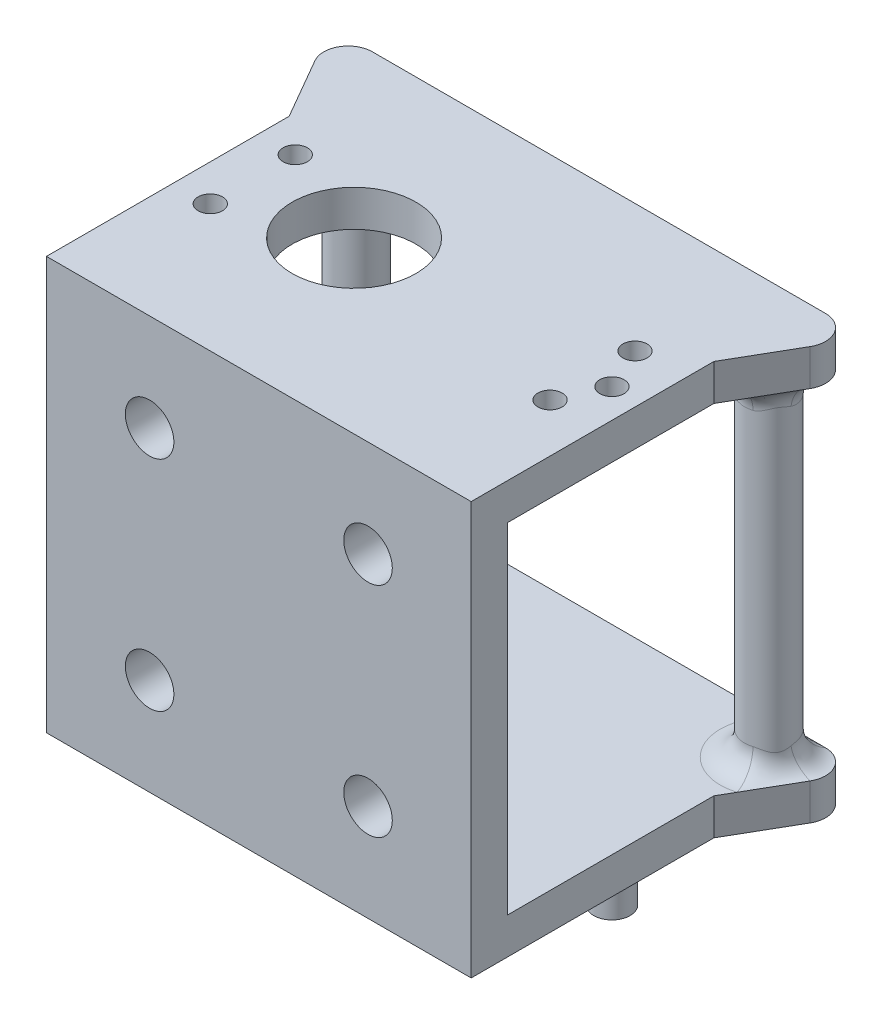
SolidWorks part; units mm, degrees
ref_plane "前视基准面" through (0, 0, 0) normal (0, 0, 1) x (1, 0, 0)
ref_plane "上视基准面" through (0, 0, 0) normal (0, 1, 0) x (1, 0, 0)
ref_plane "右视基准面" through (0, 0, 0) normal (1, 0, 0) x (0, 0, -1)
sketch "草图1" plane through (0, 0, 0) normal (0, 1, 0) x (1, 0, 0)
  line L0 (-67.7789, 0) -> (67.7789, 0) construction
  line L1 (0, 56.3618) -> (0, -56.3618) construction
  line L2 (-17, -12) -> (18, -12)
  line L6 (-21.6353, 8.0286) -> (-17, 0)
  line L7 (-17, 0) -> (-17, -12)
  line L8 (16, -6) -> (-17, -6) construction
  line L9 (-11.5, 10.0448) -> (-11.5, -22.0448) construction
  line L10 (18, -12) -> (18, 0)
  line L11 (18, 0) -> (22.6353, 8.0286)
  line L12 (-21.6353, 8.0286) -> (22.6353, 8.0286)
  circle A0 centre (14, -2.5) radius 1
  circle A1 centre (14, -9.5) radius 1
  circle A2 centre (-14, -9.5) radius 1
  circle A3 centre (-14, -2.5) radius 1
  circle A6 centre (-5.65, -6) radius 5.1
  circle A7 centre (15.6, -6) radius 1
  point P4 (0, 0)
  point P8 (0, 0)
  point P27 (-11.5, -6)
  dimension "D2" = 2
  dimension "D8" = 21.25
  dimension "D7" = 10.2
  dimension "D10" = 2
  dimension "D1" = 35
  dimension "D3" = 28
  dimension "D4" = 7
  dimension "D5" = 17
  dimension "D6" = 11.5
  dimension "D9" = 150
  dimension "D11" = 150
extrude "凸台-拉伸1" add sketch "草图1" along normal blind 3
sketch "草图2" plane through (0, 3, 0) normal (0, 1, 0) x (1, 0, 0)
  line L0 (-17, -12) -> (18, -12)
  line L1 (-17, -12) -> (18, -12) construction
  line L2 (18, -12) -> (18, -17)
  line L3 (18, -17) -> (-17, -17)
  line L4 (-17, -17) -> (-17, -12)
  dimension "D1" = 5
extrude "凸台-拉伸2" add sketch "草图2" against normal blind 3
ref_plane "基准面1" through (0, -28, 0) normal (0, -1, 0) x (-1, 0, 0)
sketch "草图3" plane through (0, -28, 0) normal (0, -1, 0) x (-1, 0, 0)
  line L6 (17, -17) -> (17, 0)
  line L7 (17, 0) -> (21.6353, 8.0286)
  line L8 (21.6353, 8.0286) -> (-22.6353, 8.0286)
  line L9 (-22.6353, 8.0286) -> (-18, 0)
  line L10 (-18, 0) -> (-18, -17)
  line L11 (-18, -17) -> (17, -17)
  line L12 (17, -17) -> (17, 0)
  line L13 (17, 0) -> (21.6353, 8.0286)
  line L14 (21.6353, 8.0286) -> (-22.6353, 8.0286)
  line L15 (-22.6353, 8.0286) -> (-18, 0)
  line L16 (-18, 0) -> (-18, -17)
  line L17 (-18, -17) -> (17, -17)
  circle A2 centre (5.65, -6) radius 1.5
  circle A3 centre (-15.6, -6) radius 1.5
  dimension "D2" = 3
  dimension "D3" = 3
  dimension "D1" = 0
extrude "凸台-拉伸3" add sketch "草图3" along normal blind 3 separate body
sketch "草图4" plane through (0, 0, 17) normal (0, 0, 1) x (1, 0, 0)
  line L5 (18, -31) -> (-17, -31) construction
  line L7 (-17, 0) -> (-17, 3) construction
  line L8 (-17, 3) -> (18, 3)
  line L9 (-17, 3) -> (-17, -31)
  line L10 (-17, -31) -> (18, -31)
  line L11 (18, 3) -> (18, -31)
  line L12 (18, -31) -> (18, -28) construction
extrude "凸台-拉伸4" add sketch "草图4" along normal blind 3
sketch "草图5" plane through (0, -28, 0) normal (0, 1, 0) x (1, 0, 0)
  line L6 (0.5, -20) -> (0.5, 16.465) construction
  line L7 (-17, -20) -> (18, -20) construction
  line L13 (22.6353, 8.0286) -> (-21.6353, 8.0286) construction
  circle A0 centre (-16.5, 5.0286) radius 2
  circle A1 centre (17.5, 5.0286) radius 2
  dimension "D1" = 4
  dimension "D2" = 17
  dimension "D3" = 3
extrude "凸台-拉伸6" add sketch "草图5" along normal up to next
extrude "凸台-拉伸7" add sketch "草图3<2>" along normal blind 6 contours A3 | A2 region at (-5.65, -28, 6) region at (15.6, -28, 6)
sketch "草图3<2>" plane through (0, -28, 0) normal (0, -1, 0) x (-1, 0, 0) same geometry as "草图3"
fillet "圆角1" radius 2 4 edges at (-21.6353, -29.5, -8.0286) (-21.6353, 1.5, -8.0286) (22.6353, -29.5, -8.0286) (22.6353, 1.5, -8.0286)
fillet "圆角2" radius 2 4 edges at (-16.5, 0, -3.0286) (17.5, 0, -3.0286) (-16.5, -28, -7.0286) (17.5, -28, -7.0286)
sketch "草图7" plane through (0, 0, 20) normal (0, 0, 1) x (1, 0, 0)
  line L0 (-17, -14) -> (18, -14) construction
  line L1 (-17, 3) -> (-17, -31) construction
  line L2 (18, -31) -> (18, 3) construction
  line L3 (0.5, 3) -> (0.5, -31) construction
  line L4 (18, 3) -> (-17, 3) construction
  line L5 (-17, -31) -> (18, -31) construction
  circle A0 centre (9.5, -5) radius 2
  circle A1 centre (9.5, -23) radius 2
  circle A2 centre (-8.5, -23) radius 2
  circle A3 centre (-8.5, -5) radius 2
  dimension "D1" = 4
  dimension "D2" = 9
  dimension "D3" = 9
extrude "切除-拉伸1" cut sketch "草图7" against normal blind 10
